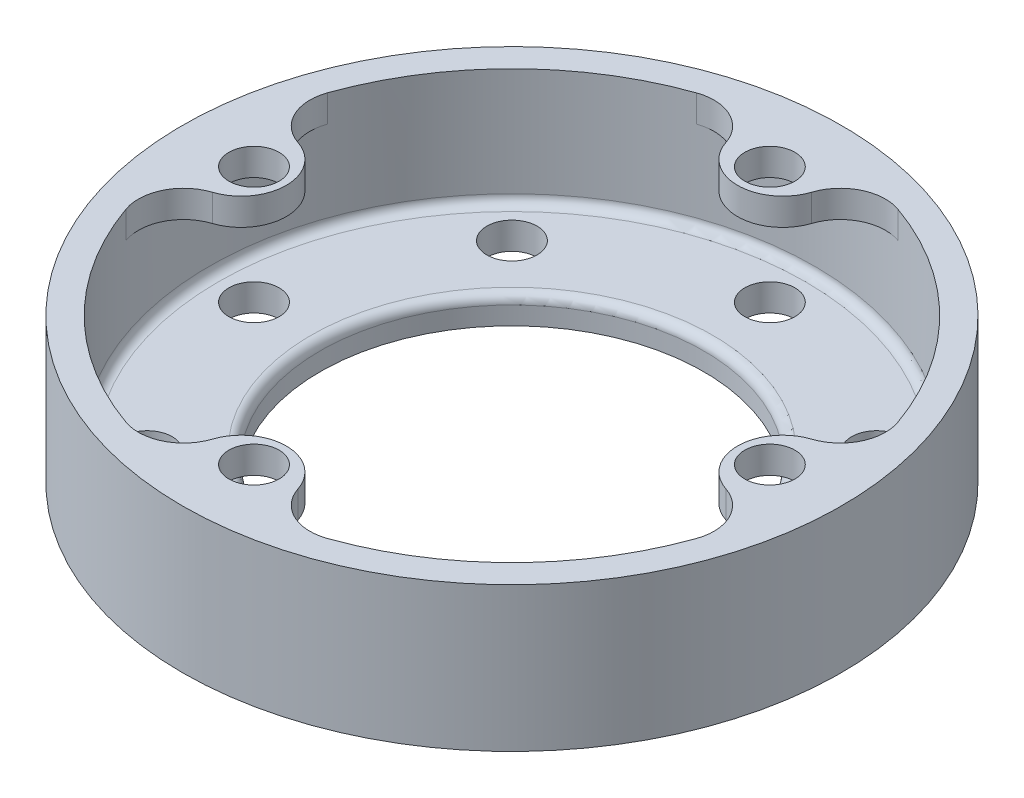
SolidWorks part; units mm, degrees
material "PW20:29:Sc:0:"
ref_plane "Front" through (0, 0, 0) normal (0, 0, 1) x (1, 0, 0)
ref_plane "Top" through (0, 0, 0) normal (0, 1, 0) x (1, 0, 0)
ref_plane "Right" through (0, 0, 0) normal (1, 0, 0) x (0, 0, -1)
sketch "Sketch1" plane through (0, 0, 0) normal (0, 1, 0) x (1, 0, 0)
  circle A0 centre (0, 0) radius 73.025
  dimension "D1" = 146.05
extrude "Base-Extrude" add sketch "Sketch1" along normal blind 32
shell "Shell1" thickness 6 removed face at (0, 32, 73.025)
sketch "Sketch4" plane through (0, 6, 0) normal (0, 1, 0) x (-1, 0, 0)
  circle A0 centre (0, 0) radius 42.5
  dimension "D1" = 85
extrude "Cut-Extrude2" cut sketch "Sketch4" against normal through all
sketch "Sketch2" plane through (0, 32, 0) normal (0, 1, 0) x (-1, 0, 0)
  line L0 (0, -73.025) -> (0, 73.025) construction
  line L1 (-10, -66.2748) -> (-10, -60)
  line L2 (10, -60) -> (10, -66.2748)
  circle A0 centre (0, 0) radius 73.025 construction
  arc A1 (-10, -66.2748) -> (10, -66.2748) centre (0, 0) ccw
  circle A2 centre (0, 0) radius 67.025 construction
  arc A3 (-10, -60) -> (10, -60) centre (0, -60) cw
  point P16 (1.5702, -0.6869)
  dimension "D2" = 10
  dimension "D1" = 60
extrude "Boss-Extrude1" add sketch "Sketch2" against normal blind 6
sketch "Sketch3" plane through (0, 32, 0) normal (0, 1, 0) x (-1, 0, 0)
  circle A0 centre (0, -57.15) radius 5.5563
  circle A1 centre (0, 0) radius 73.025 construction
  arc A2 (10, -60) -> (-10, -60) centre (0, -60) ccw construction
  point P2 (0, 0)
  point P3 (0, 0)
  point P4 (0, 0)
  point P5 (0, -57.15)
  dimension "D1" = 11.1125
  dimension "D3" = 2.85
  dimension "D2" = 57.15
extrude "Cut-Extrude1" cut sketch "Sketch3" against normal up to next
fillet "Fillet1" radius 10 2 edges at (10, 29, -66.2748) (-10, 29, -66.2748)
pattern_circular "CirPattern1" count 4 every 90 about axis through (0, 32, 0) along (0, -1, 0) of "Fillet1", "Boss-Extrude1", "Cut-Extrude1" reverse direction yes
sketch "Sketch5" plane through (0, 6, 0) normal (0, 1, 0) x (-1, 0, 0)
  circle A0 centre (0, -57.15) radius 5.5563 construction
  circle A1 centre (0, -57.15) radius 5.5562
extrude "Cut-Extrude3" cut sketch "Sketch5" against normal through all
pattern_circular "CirPattern2" count 8 every 45 about axis through (0, 32, 0) along (0, -1, 0) of "Cut-Extrude3"
fillet "Fillet2" radius 2 2 edges at (0, 6, 67.025) (0, 6, 42.5)
